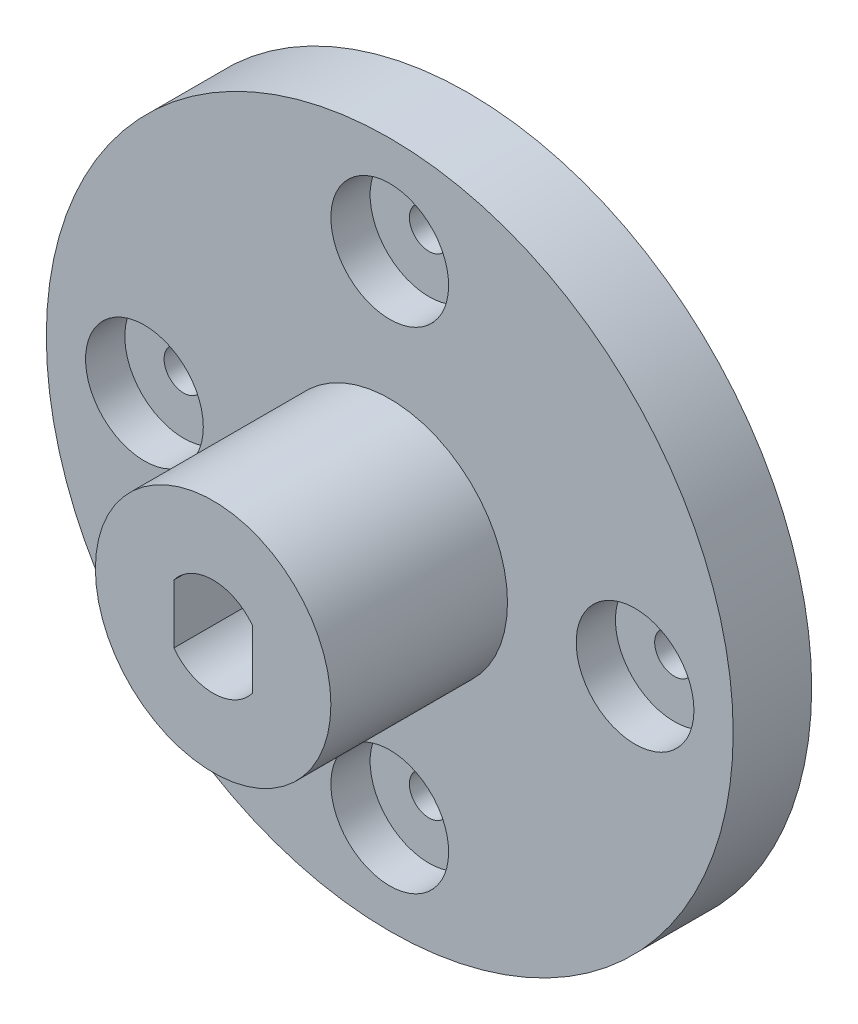
SolidWorks part; units mm, degrees
ref_plane "Front Plane" through (0, 0, 0) normal (0, 0, 1) x (1, 0, 0)
ref_plane "Top Plane" through (0, 0, 0) normal (0, 1, 0) x (1, 0, 0)
ref_plane "Right Plane" through (0, 0, 0) normal (1, 0, 0) x (0, 0, -1)
sketch "Sketch1" plane through (0, 0, 0) normal (0, 0, 1) x (1, 0, 0)
  line L1 (-2, 1.5) -> (-2, -1.5)
  line L2 (2, 1.5) -> (2, -1.5)
  circle A0 centre (0, 0) radius 17.5
  circle A1 centre (0, 0) radius 6
  arc A2 (-2, -1.5) -> (2, -1.5) centre (0, 0) ccw
  arc A3 (2, 1.5) -> (-2, 1.5) centre (0, 0) ccw
  circle A4 centre (0, 0) radius 1.5
  circle A7 centre (0, 12.5) radius 1
  circle A8 centre (12.5, 0) radius 1
  circle A9 centre (0, -12.5) radius 1
  circle A10 centre (-12.5, 0) radius 1
  circle A12 centre (0, 12.5) radius 3
  circle A13 centre (12.5, 0) radius 3
  circle A14 centre (0, -12.5) radius 3
  circle A15 centre (-12.5, 0) radius 3
  point P8 (0, 0)
  point P11 (-2, 0)
  point P14 (2, 0)
  point P24 (0, 0)
  point P32 (0, 0)
  dimension "D1" = 35
  dimension "D2" = 12
  dimension "D3" = 4
  dimension "D4" = 4
  dimension "D5" = 2
  dimension "D6" = 6
extrude "Boss-Extrude1" add sketch "Sketch1" against normal blind 4 contours A15 A10 | A0 A15 A14 A13 A12 A1 | A12 A7 | A13 A8 | A1 A3 L2 A2 L1 | A14 A9 | L2 A3 L1 A2 A4 region at (0, 2.436, 0) region at (-17.005, 0, 0) region at (-5.8303, 0, 0) region at (-2.9151, 12.5, 0) region at (9.5849, 0, 0) region at (-2.9151, -12.5, 0) region at (-15.4151, 0, 0)
extrude "Boss-Extrude2" add sketch "Sketch1<3>" along normal blind 9 separate body contours A1 A3 L2 A2 L1 region at (-5.8303, 0, 0)
sketch "Sketch1<3>" plane through (0, 0, 0) normal (0, 0, 1) x (1, 0, 0) same geometry as "Sketch1"
sketch "Sketch2" plane through (0, 0, -4) normal (0, 0, -1) x (-1, 0, 0)
  circle A0 centre (0, 0) radius 2.5
extrude "Cut-Extrude1" cut sketch "Sketch2" against normal blind 2
extrude "Cut-Extrude2" cut sketch "Sketch1<6>" against normal blind 2 contours A15 A10 | A14 A9 | A13 A8 | A12 A7 region at (-2.9151, 12.5, 0) region at (9.5849, 0, 0) region at (-2.9151, -12.5, 0) region at (-15.4151, 0, 0)
sketch "Sketch1<6>" plane through (0, 0, 0) normal (0, 0, 1) x (1, 0, 0) same geometry as "Sketch1"
